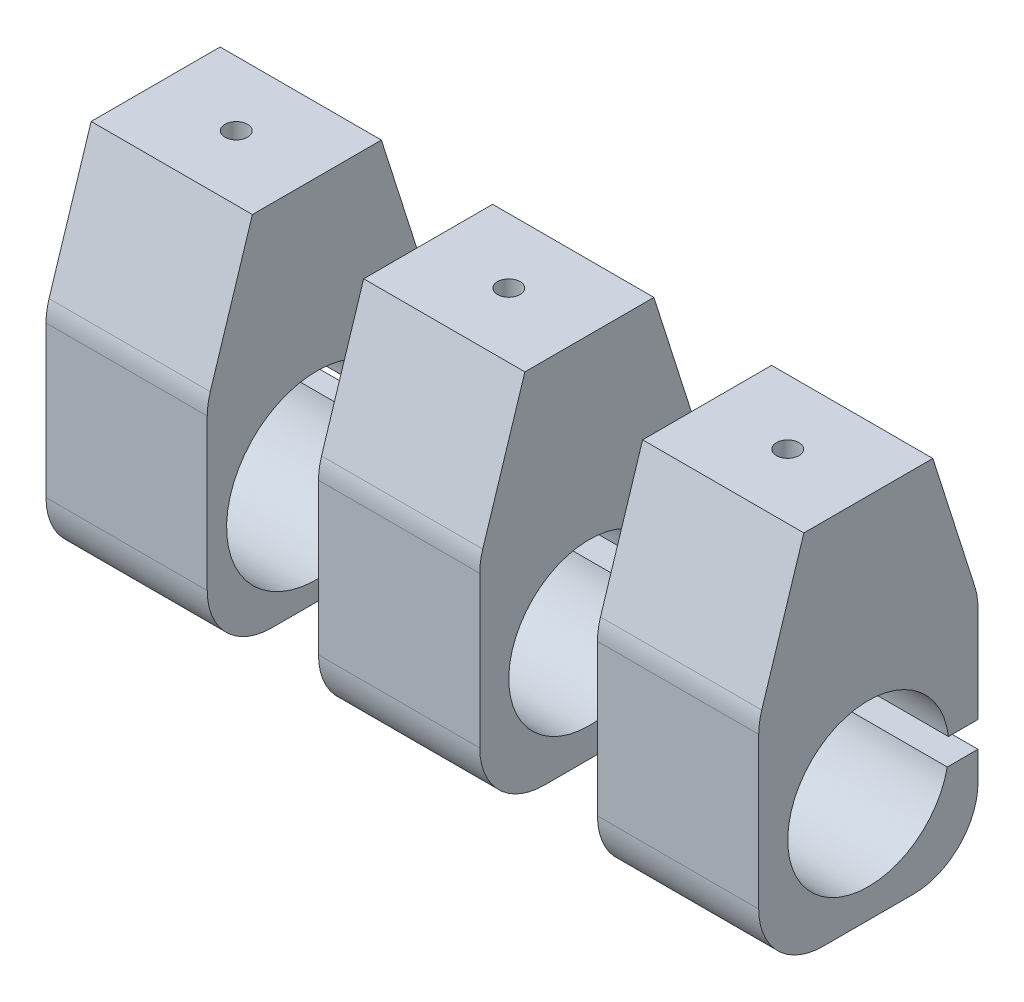
SolidWorks part; units mm, degrees
ref_plane "Front Plane" through (0, 0, 0) normal (0, 0, 1) x (1, 0, 0)
ref_plane "Top Plane" through (0, 0, 0) normal (0, 1, 0) x (1, 0, 0)
ref_plane "Right Plane" through (0, 0, 0) normal (1, 0, 0) x (0, 0, -1)
sketch "Sketch1" plane through (0, 0, 0) normal (1, 0, 0) x (0, 0, -1)
  line L0 (-10, 40) -> (10, 40)
  line L1 (10, 40) -> (17, 18)
  line L2 (17, 18) -> (17, -17)
  line L3 (17, -17) -> (-17, -17)
  line L4 (-17, -17) -> (-17, 18)
  line L5 (-17, 18) -> (-10, 40)
  line L6 (17, 1.45) -> (12.4156, 1.45)
  line L7 (17, -2.55) -> (12.2371, -2.55)
  line L9 (19, 19) -> (-19, 19) construction
  circle A0 centre (0, 0) radius 14
  circle A1 centre (0, 0) radius 12.5
  point P6 (0, 40)
  point P15 (14.6186, -2.55)
  dimension "D2" = 25
  dimension "D3" = 28
  dimension "D1" = 20
  dimension "D4" = 17
  dimension "D5" = 35
  dimension "D6" = 17
  dimension "D7" = 22
  dimension "D8" = 4
  dimension "D9" = 17.55
extrude "zoom lense mount" add sketch "Sketch1" along normal blind 25 contours L5 L4 L3 L2 L1 L0 A0 region at (0, 14.9335, 0.1637)
extrude "spec mount1" add sketch "Sketch1<4>" along normal blind 25 from offset 42.25 separate body contours A0 A1 | L5 L4 L3 L2 L1 L0 A0 region at (0, 14.9335, 0.1637) region at (0, 1.8454, -13.1702)
sketch "Sketch1<4>" plane through (0, 0, 0) normal (1, 0, 0) x (0, 0, -1) same geometry as "Sketch1"
extrude "spec mount 2" add sketch "Sketch1<5>" along normal blind 25 from offset 85.5 separate body contours L5 L4 L3 L2 L1 L0 A0 | A0 A1 region at (0, 14.9335, 0.1637) region at (0, 1.8454, -13.1702)
sketch "Sketch1<5>" plane through (0, 0, 0) normal (1, 0, 0) x (0, 0, -1) same geometry as "Sketch1"
fillet "Fillet1" radius 10 4 edges at (12.5, -17, -17) (12.5, 18, -17) (12.5, -17, 17) (12.5, 18, 17)
fillet "Fillet2" radius 10 4 edges at (54.75, -17, -17) (54.75, 18, -17) (54.75, -17, 17) (54.75, 18, 17)
fillet "Fillet3" radius 10 4 edges at (98, -17, -17) (98, 18, -17) (98, -17, 17) (98, 18, 17)
sketch "Sketch2" plane through (0, 40, 0) normal (0, 1, 0) x (1, 0, 0)
  line L0 (85.5, -10) -> (85.5, 10) construction
  circle A0 centre (98, 0) radius 1.75
  dimension "D2" = 3.5
  dimension "D1" = 12.5
extrude "Cut-Extrude1" cut sketch "Sketch2" against normal blind 30
sketch "Sketch3" plane through (0, 40, 0) normal (0, 1, 0) x (1, 0, 0)
  line L0 (67.25, -10) -> (67.25, 10) construction
  circle A0 centre (54.75, 0) radius 1.75
  dimension "D2" = 3.5
  dimension "D1" = 12.5
extrude "Cut-Extrude2" cut sketch "Sketch3" against normal blind 30
sketch "Sketch4" plane through (0, 40, 0) normal (0, 1, 0) x (1, 0, 0)
  line L0 (0, -10) -> (0, 10) construction
  circle A0 centre (12.5, 0) radius 1.75
  dimension "D2" = 3.5
  dimension "D1" = 12.5
extrude "Cut-Extrude3" cut sketch "Sketch4" against normal blind 30
